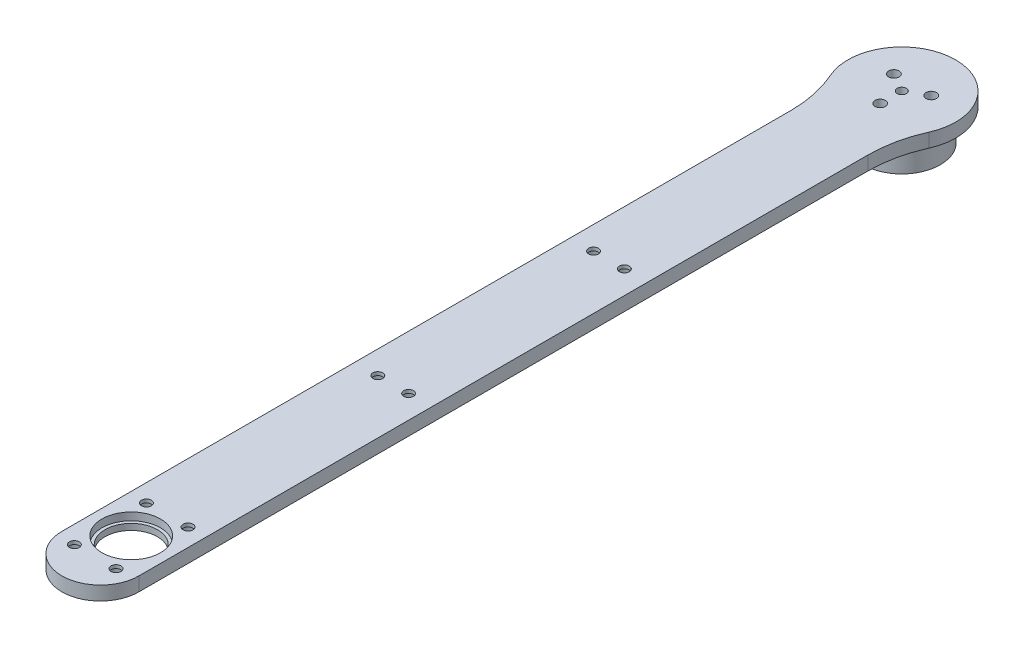
SolidWorks part; units mm, degrees
other "마크업1"
sketch "스케치14" plane through (-17.5, 12, -17.5) normal (-0.0092, 0.8478, -0.5302) x (0.9606, -0.1397, -0.2401)
sketch "스케치15" plane through (-17.5, 12, -17.5) normal (-0.0092, 0.8478, -0.5302) x (0.9606, -0.1397, -0.2401)
sketch "스케치16" plane through (-17.5, 12, -17.5) normal (-0.0092, 0.8478, -0.5302) x (0.9606, -0.1397, -0.2401)
sketch "스케치17" plane through (-17.5, 12, -17.5) normal (-0.0092, 0.8478, -0.5302) x (0.9606, -0.1397, -0.2401)
sketch "스케치18" plane through (-17.5, 11, -17.5) normal (-0.0092, 0.8478, -0.5302) x (0.9606, -0.1397, -0.2401)
sketch "스케치19" plane through (-17.5, 11, -17.5) normal (-0.0092, 0.8478, -0.5302) x (0.9606, -0.1397, -0.2401)
sketch "스케치20" plane through (-17.5, 11, -17.5) normal (-0.0092, 0.8478, -0.5302) x (0.9606, -0.1397, -0.2401)
sketch "스케치21" plane through (-17.5, 11, -17.5) normal (-0.0092, 0.8478, -0.5302) x (0.9606, -0.1397, -0.2401)
sketch "스케치22" plane through (-17.5, 11, -17.5) normal (-0.0092, 0.8478, -0.5302) x (0.9606, -0.1397, -0.2401)
sketch "스케치24" plane through (-17.5, 11, -17.5) normal (-0.0092, 0.8478, -0.5302) x (0.9606, -0.1397, -0.2401)
sketch "스케치25" plane through (-17.5, 11, -17.5) normal (-0.0092, 0.8478, -0.5302) x (0.9606, -0.1397, -0.2401)
sketch "스케치27" plane through (-17.5, 4.5, -17.5) normal (-0.0092, 0.8478, -0.5302) x (0.9606, -0.1397, -0.2401)
sketch "스케치35" plane through (-17.5, 4.5, -17.5) normal (-0.0092, 0.8478, -0.5302) x (0.9606, -0.1397, -0.2401)
sketch "스케치38" plane through (-17.5, 4.5, -17.5) normal (-0.0092, 0.8478, -0.5302) x (0.9606, -0.1397, -0.2401)
sketch "스케치40" plane through (-17.5, 4.5, -17.5) normal (-0.0092, 0.8478, -0.5302) x (0.9606, -0.1397, -0.2401)
material "7075-T6 (SN)"
ref_plane "정면" through (0, 0, 0) normal (0, 0, 1) x (1, 0, 0)
ref_plane "윗면" through (0, 0, 0) normal (0, 1, 0) x (1, 0, 0)
ref_plane "우측면" through (0, 0, 0) normal (1, 0, 0) x (0, 0, -1)
sketch "스케치1" plane through (0, 0, 0) normal (0, 1, 0) x (1, 0, 0)
  line L0 (-12.5, -260) -> (-12.5, -12.2474)
  line L1 (0, 0) -> (0, -260) construction
  line L2 (12.5, -260) -> (12.5, -12.2474)
  arc A1 (12.5, -12.2474) -> (-12.5, -12.2474) centre (0, 0) ccw
  arc A2 (-12.5, -260) -> (12.5, -260) centre (0, -260) ccw
  dimension "D2" = 35
  dimension "D3" = 25
  dimension "D4" = 260
extrude "보스-돌출1" add sketch "스케치1" along normal blind 9
sketch "스케치3" plane through (0, 9, 0) normal (0, 1, 0) x (1, 0, 0)
  circle A0 centre (0, 0) radius 13.5
  dimension "D1" = 27
extrude "보스-돌출2" add sketch "스케치3" along normal blind 2 contours A0 region at (0, 9, 0)
sketch "스케치4" plane through (0, 0, 0) normal (0, -1, 0) x (1, 0, 0)
  circle A0 centre (0, 0) radius 13.5
  dimension "D1" = 27
extrude "보스-돌출3" add sketch "스케치4" along normal blind 3 contours A0 region at (0, 0, 0)
sketch "스케치5" plane through (0, 9, 0) normal (0, 1, 0) x (1, 0, 0)
  circle A0 centre (0, -250) radius 9.5
  dimension "D1" = 19
  dimension "D2" = 250
extrude "컷-돌출2" cut sketch "스케치5" against normal through all
sketch "스케치7" plane through (0, -3, 0) normal (0, -1, 0) x (1, 0, 0)
  circle A0 centre (0, 0) radius 7
  point P3 (0, 7)
  dimension "D1" = 14
hole_wizard "M3 육각 소켓 머리 캡 나사용 카운터보어4" positions "스케치8" profile "스케치10" counterbore size "M3" standard "ISO" end condition through all
sketch "스케치8" plane through (0, -3, 0) normal (0, -1, 0) x (-1, 0, 0)
  point P0 (0, -7)
sketch "스케치10" plane through (0, -3, 7) normal (1, 0, 0) x (0, 0, -1)
  line L0 (0, 0) -> (0, 14)
  line L1 (0, 14) -> (1.7, 14)
  line L3 (1.7, 14) -> (1.7, 3.4)
  line L4 (1.7, 3.4) -> (3.25, 3.4)
  line L5 (3.25, 3.4) -> (3.25, 0)
  line L7 (3.25, 0) -> (0, 0)
  line L11 (0, -6.35) -> (0, 107.95) construction
  dimension "관통 구멍 지름" = 3.4
  dimension "관통 구멍 깊이" = 14
  dimension "카운터보어 지름" = 6.5
  dimension "카운터보어 깊이" = 3.4
pattern_circular "원형 패턴1" count 3 over 360 about axis through (0, 9, 0) along (0, -1, 0) of "M3 육각 소켓 머리 캡 나사용 카운터보어4"
sketch "스케치11" plane through (0, -3, 0) normal (0, -1, 0) x (1, 0, 0)
  circle A0 centre (0, 0) radius 12.5
  circle A1 centre (6.0622, -3.5) radius 3.25 construction
  circle A2 centre (0, 0) radius 13.5
  circle A3 centre (0, 0) radius 13.5
  circle A4 centre (-6.0622, -3.5) radius 3.25 construction
  circle A5 centre (0, 7) radius 3.25 construction
  circle A6 centre (6.0622, -3.5) radius 3.25
  circle A7 centre (-6.0622, -3.5) radius 3.25
  circle A8 centre (0, 7) radius 3.25
  circle M1 centre (6.0622, -3.5) radius 3.25
  circle M2 centre (-6.0622, -3.5) radius 3.25
  circle M3 centre (0, 7) radius 3.25
  dimension "D1" = 25
  dimension "D2" = 0
extrude "보스-돌출4" add sketch "스케치11" along normal blind 7 contours A0 M1 M3 M2 region at (0, -3, 0)
sketch "스케치13" plane through (0, 11, 0) normal (0, 1, 0) x (1, 0, 0)
  circle A0 centre (0, 0) radius 11
  dimension "D1" = 22
extrude "컷-돌출3" cut sketch "스케치13" against normal blind 3
fillet "필렛1" radius 40 2 edges at (12.5, 4.5, 12.2474) (-12.5, 4.5, 12.2474)
sketch "스케치23" plane through (0, -10, 0) normal (0, -1, 0) x (1, 0, 0)
  circle A0 centre (0, 0) radius 11
  dimension "D1" = 22
extrude "컷-돌출4" [suppressed] cut sketch "스케치23" against normal blind 5
sketch "스케치26" plane through (0, 0, 0) normal (0, 0, 1) x (1, 0, 0)
  line L1 (-32.4505, 21.3151) -> (32.6856, 21.3151)
  line L2 (-32.4505, 21.3151) -> (-32.4505, 4.5)
  line L3 (-32.4505, 4.5) -> (32.6856, 4.5)
  line L4 (32.6856, 21.3151) -> (32.6856, 4.5)
  line L6 (-33.8554, 0) -> (36.1825, 0) construction
  line L7 (-13.5, 0) -> (13.5, 0) construction
  dimension "D1" = 4.5
extrude "컷-돌출5" cut sketch "스케치26" against normal mid plane 2222
sketch "스케치28" plane through (0, 0, 0) normal (0, -1, 0) x (1, 0, 0)
  circle A0 centre (0, 250) radius 8.5
  circle A1 centre (0, 250) radius 9.5 construction
  circle A2 centre (0, 250) radius 9.5
  dimension "D1" = 17
extrude "보스-돌출5" add sketch "스케치28" against normal blind 2
sketch "스케치29" plane through (0, 0, 0) normal (0, -1, 0) x (1, 0, 0)
  line L0 (-19.9182, 250) -> (29.4679, 250) construction
  line L1 (0, 250) -> (-16.2219, 278.0971) construction
  circle A0 centre (0, 250) radius 13.5 construction
  circle A1 centre (0, 250) radius 8.5 construction
  point P6 (-6.75, 261.6913)
  dimension "D1" = 27
  dimension "D2" = 60
sketch "스케치32" plane through (0, 0, 0) normal (0, -1, 0) x (1, 0, 0)
  line L0 (-33.4559, 0) -> (57.4354, 0) construction
  line L1 (-63.5769, 25) -> (71.4391, 25) construction
  line L2 (-5, 57.8431) -> (-5, -39.9238) construction
  line L3 (0, 97.6838) -> (0, -52.2429) construction
  dimension "D1" = 25
  dimension "D2" = 5
hole_wizard "M3 육각 소켓 머리 캡 나사용 카운터보어2" positions "스케치33" profile "스케치34" counterbore size "M3" standard "ISO" end condition through all
sketch "스케치33" plane through (0, 0, 0) normal (0, -1, 0) x (-1, 0, 0)
  line L0 (63.5769, -25) -> (-71.4391, -25) construction
  line L1 (5, -57.8431) -> (5, 39.9238) construction
  point P0 (5, -25)
sketch "스케치34" plane through (-5, 0, 25) normal (1, 0, 0) x (0, 0, -1)
  line L0 (0, 0) -> (0, 4.5)
  line L1 (0, 4.5) -> (1.6, 4.5)
  line L3 (1.6, 4.5) -> (1.6, 3.4)
  line L4 (1.6, 3.4) -> (3.25, 3.4)
  line L5 (3.25, 3.4) -> (3.25, 0)
  line L7 (3.25, 0) -> (0, 0)
  line L11 (0, -6.35) -> (0, 107.95) construction
  dimension "관통 구멍 지름" = 3.2
  dimension "관통 구멍 깊이" = 4.5
  dimension "카운터보어 지름" = 6.5
  dimension "카운터보어 깊이" = 3.4
pattern_linear "선형 패턴1" count 3 spacing 70 along (0, 0, 1) count 2 spacing 10 along (1, 0, 0) of "M3 육각 소켓 머리 캡 나사용 카운터보어2"
hole_wizard "M3 육각 소켓 머리 캡 나사용 카운터보어3" positions "스케치36" profile "스케치37" counterbore size "M3" standard "ISO" end condition through all
sketch "스케치36" plane through (0, 0, 0) normal (0, -1, 0) x (-1, 0, 0)
  point P0 (6.75, -261.6913)
sketch "스케치37" plane through (-6.75, 0, 261.6913) normal (1, 0, 0) x (0, 0, -1)
  line L0 (0, 0) -> (0, 4.5)
  line L1 (0, 4.5) -> (1.6, 4.5)
  line L3 (1.6, 4.5) -> (1.6, 3.4)
  line L4 (1.6, 3.4) -> (3.25, 3.4)
  line L5 (3.25, 3.4) -> (3.25, 0)
  line L7 (3.25, 0) -> (0, 0)
  line L11 (0, -6.35) -> (0, 107.95) construction
  dimension "관통 구멍 지름" = 3.2
  dimension "관통 구멍 깊이" = 4.5
  dimension "카운터보어 지름" = 6.5
  dimension "카운터보어 깊이" = 3.4
pattern_circular "원형 패턴2" count 6 over 360 about axis through (0, 2, 250) along (0, -1, 0) skipping 1, 4 of "M3 육각 소켓 머리 캡 나사용 카운터보어3"
sketch "스케치39" plane through (0, 0, 0) normal (0, -1, 0) x (1, 0, 0)
  circle A0 centre (5, 25) radius 3.25
  circle A1 centre (5, 25) radius 3.25 construction
  circle A2 centre (-5, 25) radius 3.25
  circle A3 centre (-5, 25) radius 3.25 construction
extrude "보스-돌출6" add sketch "스케치39" against normal blind 4.5
hole_wizard "Ø3.0mm 맞춤핀 구멍1" positions "스케치41" profile "스케치42" hole size "Ø3.0" standard "ISO"
sketch "스케치41" plane through (0, 4.5, 0) normal (0, 1, 0) x (1, 0, 0)
  point P0 (0, 0)
sketch "스케치42" plane through (0, 4.5, 0) normal (1, 0, 0) x (0, 0, 1)
  line L0 (0, 0) -> (0, 5.9013)
  line L1 (0, 5.9013) -> (1.5, 5)
  line L2 (1.5, 5) -> (1.5, 0)
  line L5 (1.5, 0) -> (0, 0)
  line L10 (0, 5.9013) -> (-1.5, 5) construction
  line L11 (0, -6.35) -> (0, 107.95) construction
  dimension "구멍 지름" = 3
  dimension "구멍 깊이" = 5
  dimension "드릴 각도" = 118
